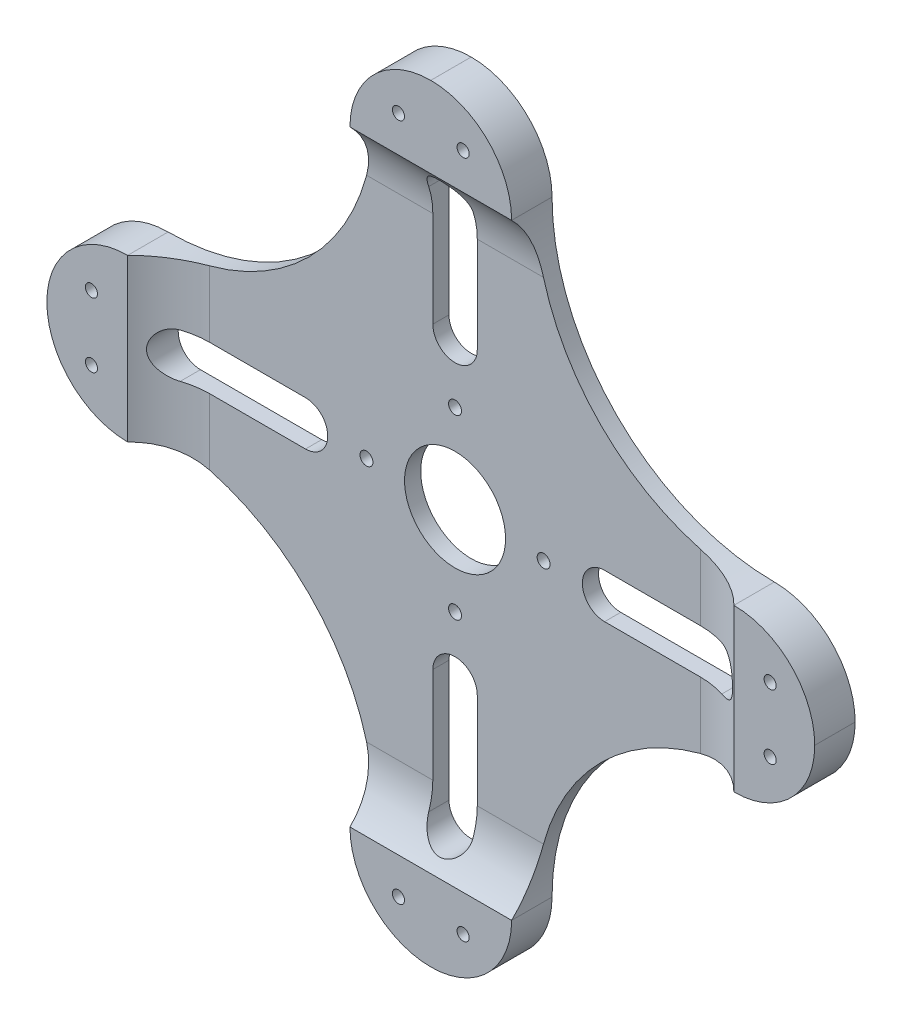
SolidWorks part; units mm, degrees
ref_plane "Front Plane" through (0, 0, 0) normal (0, 0, 1) x (1, 0, 0)
ref_plane "Top Plane" through (0, 0, 0) normal (0, 1, 0) x (1, 0, 0)
ref_plane "Right Plane" through (0, 0, 0) normal (1, 0, 0) x (0, 0, -1)
sketch "Sketch1" plane through (0, 0, 0) normal (0, 0, 1) x (1, 0, 0)
  line L13 (-95, -95) -> (95, -95)
  line L14 (-95, -95) -> (-95, 95)
  line L15 (-95, 95) -> (95, 95)
  line L16 (95, -95) -> (95, 95)
  line L17 (-95, -95) -> (95, 95) construction
  line L18 (-95, 95) -> (95, -95) construction
  line L19 (-75, -75) -> (75, -75)
  line L20 (-75, -75) -> (-75, 75)
  line L21 (-75, 75) -> (75, 75)
  line L22 (75, -75) -> (75, 75)
  line L23 (-75, -75) -> (75, 75) construction
  line L24 (-75, 75) -> (75, -75) construction
  line L39 (-75, -24.9122) -> (-75, 26.5574)
  line L48 (-95, -20.0021) -> (-75, -20.0021)
  line L49 (-75, -20.0021) -> (-75, 20.0021)
  line L50 (-75, 20.0021) -> (-95, 20.0021)
  line L51 (-95, 20.0021) -> (-95, -20.0021)
  line L64 (-72, -72) -> (-72, 72)
  line L65 (-72, 72) -> (72, 72)
  line L70 (72, -72) -> (72, 72)
  line L71 (-72, -72) -> (72, -72)
  line L72 (-10.5, -75) -> (10.5, -75)
  line L77 (75, -10.5) -> (64, -10.5)
  line L78 (75, -10.5) -> (75, 10.5)
  line L79 (75, 10.5) -> (64, 10.5)
  line L80 (64, -10.5) -> (64, 10.5)
  line L81 (-10.5, -75) -> (-10.5, -64)
  line L82 (-10.5, -64) -> (10.5, -64)
  line L83 (10.5, -75) -> (10.5, -64)
  line L84 (-75, 10.5) -> (-75, -10.5)
  line L85 (-75, 10.5) -> (-64, 10.5)
  line L86 (-64, 10.5) -> (-64, -10.5)
  line L87 (-75, -10.5) -> (-64, -10.5)
  line L88 (10.5, 75) -> (-10.5, 75)
  line L89 (10.5, 75) -> (10.5, 64)
  line L90 (10.5, 64) -> (-10.5, 64)
  line L91 (-10.5, 75) -> (-10.5, 64)
  line L92 (-75, 45) -> (-72, 45)
  line L93 (-45, 75) -> (-45, 72)
  line L94 (-20.0021, 95) -> (-20.0021, 75)
  line L95 (-20.0021, 75) -> (20.0021, 75)
  line L96 (20.0021, 75) -> (20.0021, 95)
  line L97 (20.0021, 95) -> (-20.0021, 95)
  line L98 (95, 20.0021) -> (75, 20.0021)
  line L99 (75, 20.0021) -> (75, -20.0021)
  line L100 (75, -20.0021) -> (95, -20.0021)
  line L101 (95, -20.0021) -> (95, 20.0021)
  line L102 (20.0021, -95) -> (20.0021, -75)
  line L103 (20.0021, -75) -> (-20.0021, -75)
  line L104 (-20.0021, -75) -> (-20.0021, -95)
  line L105 (-20.0021, -95) -> (20.0021, -95)
  line L106 (-85, 20.0021) -> (-85, -20.0021) construction
  circle A12 centre (-83.9698, 8) radius 1.5
  circle A13 centre (-83.9698, -8) radius 1.5
  circle A15 centre (8, 83.9698) radius 1.5
  circle A17 centre (-8, 83.9698) radius 1.5
  circle A18 centre (83.9698, -8) radius 1.5
  circle A20 centre (83.9698, 8) radius 1.5
  circle A21 centre (-8, -83.9698) radius 1.5
  circle A23 centre (8, -83.9698) radius 1.5
  arc A24 (-75, 20.0021) -> (-20.0021, 75) centre (-75, 75) ccw
  arc A25 (20.0021, 75) -> (75, 20.0021) centre (75, 75) ccw
  arc A26 (75, -20.0021) -> (20.0021, -75) centre (75, -75) ccw
  arc A27 (-20.0021, -75) -> (-75, -20.0021) centre (-75, -75) ccw
  point P0 (0, 0)
  point P5 (-85, 0)
  point P6 (-64, 0)
  point P11 (0, 0)
  point P85 (0, 0)
  point P95 (0, 0)
  dimension "D3" = 3
  dimension "D1" = 190
  dimension "D2" = 190
  dimension "D4" = 150
  dimension "D5" = 4
  dimension "D6" = 4
  dimension "D8" = 11
  dimension "D7" = 21
  dimension "D10" = 45
  dimension "D11" = 45
  dimension "D9" = 4
extrude "Boss-Extrude1" add sketch "Sketch1" along normal blind 4 contours A24 L39 L85 L64 | L49 L87 L64 L85 | L49 L39 L50 L14 L48 A13 A12 | L64 L87 L86 L85 | A27 L64 L87 L39 | A27 L71 L81 L82 L83 A26 L70 L77 L80 L79 A25 L65 L89 L90 L91 A24 L64 L85 L86 L87 | L65 L91 L90 L89 | L21 L96 L15 L94 A17 A15 | A25 L21 L89 L65 | L21 L91 L65 L89 | A24 L65 L91 L21 | L80 L77 L70 L79 | L22 L79 L70 L77 | A26 L22 L77 L70 | A25 L70 L79 L22 | L22 L100 L16 L98 A20 A18 | A26 L71 L83 L19 | L19 L83 L71 L81 | L71 L83 L82 L81 | A27 L19 L81 L71 | L19 L104 L13 L102 A23 A21 region at (0, -85.0185, 0) region at (-85.0185, 0, 0) region at (-15.2647, -73.4979, 0) region at (-73.4979, -15.2647, 0) region at (15.2647, -73.4979, 0) region at (0, -73.5, 0) region at (0, 0, 0) region at (-73.4979, 15.2647, 0) region at (-73.5, 0, 0) region at (85.0185, 0, 0) region at (0, -68, 0) region at (0, 85.0185, 0) region at (-68, 0, 0) region at (73.4979, -15.2647, 0) region at (-15.2647, 73.4979, 0) region at (73.4979, 15.2647, 0) region at (73.5, 0, 0) region at (68, 0, 0) region at (15.2647, 73.4979, 0) region at (0, 73.5, 0) region at (0, 68, 0)
sketch "Sketch6" plane through (0, 0, 0) normal (0, 0, 1) x (1, 0, 0)
  line L7 (0, 37) -> (0, 67) construction
  line L16 (-5.5, 37) -> (-5.5, 67)
  line L18 (5.5, 37) -> (5.5, 67)
  line L29 (37, -5.5) -> (67, -5.5)
  line L30 (37, 5.5) -> (67, 5.5)
  line L35 (37, 0) -> (67, 0) construction
  line L36 (-5.5, -37) -> (-5.5, -67)
  line L37 (5.5, -37) -> (5.5, -67)
  line L40 (0, -37) -> (0, -67) construction
  line L43 (-37, 5.5) -> (-67, 5.5)
  line L46 (-37, -5.5) -> (-67, -5.5)
  line L51 (-37, 0) -> (-67, 0) construction
  arc A3 (-5.5, 37) -> (5.5, 37) centre (0, 37) ccw
  arc A12 (75, 20.9897) -> (20.9897, 75) centre (93.8629, 93.8629) cw
  arc A13 (5.5, 67) -> (-5.5, 67) centre (0, 67) ccw
  circle A14 centre (0, 0) radius 12.5
  arc A15 (37, 5.5) -> (37, -5.5) centre (37, 0) ccw
  arc A16 (67, -5.5) -> (67, 5.5) centre (67, 0) ccw
  arc A17 (5.5, -37) -> (-5.5, -37) centre (0, -37) ccw
  arc A18 (-5.5, -67) -> (5.5, -67) centre (0, -67) ccw
  arc A19 (-37, -5.5) -> (-37, 5.5) centre (-37, 0) ccw
  arc A20 (-67, 5.5) -> (-67, -5.5) centre (-67, 0) ccw
  point P2 (0, 52)
  point P13 (52, 0)
  point P23 (0, -52)
  point P31 (-52, 0)
  point P69 (-50, 0)
  dimension "D1" = 52
  dimension "D2" = 25
  dimension "D3" = 11
  dimension "D4" = 30
extrude "Cut-Extrude15" cut sketch "Sketch6" against normal mid plane 10 contours A12 | L43 A20 L46 A19 | A14 | L30 A16 L29 A15 | A3 L18 A13 L16 | A17 L36 A18 L37
sketch "Sketch11" plane through (0, 0, 0) normal (0, 0, 1) x (1, 0, 0)
  line L0 (20.0021, 95) -> (-20.0021, 95)
  line L1 (-95, 20.0021) -> (-75, 20.0021)
  line L2 (-95, 20.0021) -> (-95, -20.0021)
  line L3 (-95, -20.0021) -> (-75, -20.0021)
  line L4 (-75, 20.0021) -> (-75, -20.0021)
  line L5 (20.0021, 95) -> (20.0021, 75)
  line L6 (20.0021, 75) -> (-20.0021, 75)
  line L7 (-20.0021, 95) -> (-20.0021, 75)
  line L8 (95, -20.0021) -> (95, 20.0021)
  line L9 (95, -20.0021) -> (75, -20.0021)
  line L10 (75, -20.0021) -> (75, 20.0021)
  line L11 (95, 20.0021) -> (75, 20.0021)
  line L12 (-20.0021, -95) -> (20.0021, -95)
  line L13 (-20.0021, -95) -> (-20.0021, -75)
  line L14 (-20.0021, -75) -> (20.0021, -75)
  line L15 (20.0021, -95) -> (20.0021, -75)
  circle A0 centre (-83.9698, 8) radius 1.5
  circle A1 centre (-83.9698, -8) radius 1.5
  circle A2 centre (8, 83.9698) radius 1.5
  circle A3 centre (-8, 83.9698) radius 1.5
  circle A4 centre (83.9698, -8) radius 1.5
  circle A5 centre (83.9698, 8) radius 1.5
  circle A6 centre (-8, -83.9698) radius 1.5
  circle A7 centre (8, -83.9698) radius 1.5
  dimension "D1" = 3
extrude "Boss-Extrude2" add sketch "Sketch11" along normal blind 6 from surface starting at face at (-52, 0, 4)
fillet "Fillet5" radius 20 8 edges at (95, -20.0021, 5) (95, 20.0021, 5) (20.0021, 95, 5) (-20.0021, 95, 5) (-95, -20.0021, 5) (-95, 20.0021, 5) (-20.0021, -95, 5) (20.0021, -95, 5)
fillet "Fillet6" radius 20 4 edges at (-75, 0, 4) (0, -75, 4) (75, 0, 4) (0, 75, 4)
sketch "Sketch10" plane through (0, 0, 0) normal (0, 0, 1) x (1, 0, 0)
  line L0 (0, 21.9203) -> (-21.9203, 0) construction
  line L5 (0, 21.9203) -> (21.9203, 0) construction
  line L7 (-21.9203, 0) -> (0, -21.9203) construction
  line L8 (21.9203, 0) -> (0, -21.9203) construction
  circle A8 centre (0, 21.9203) radius 1.6
  circle A9 centre (21.9203, 0) radius 1.6
  circle A10 centre (0, -21.9203) radius 1.6
  circle A11 centre (-21.9203, 0) radius 1.6
  dimension "D1" = 31
  dimension "D2" = 31
  dimension "D3" = 3.2
extrude "Cut-Extrude16" cut sketch "Sketch10" along normal through all both and the other way through all contours A10 | A9 | A8 | A11 region at (0, 21.9203, 0) region at (21.9203, 0, 0) region at (0, -21.9203, 0) region at (-21.9203, 0, 0)
